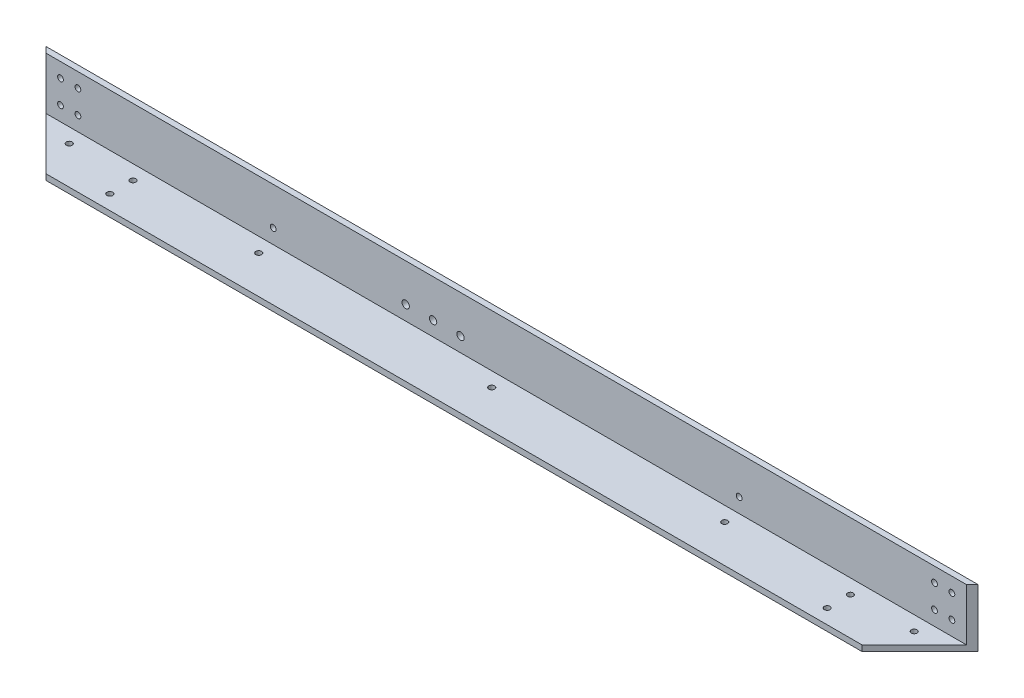
SolidWorks part; units mm, degrees
ref_plane "Front Plane" through (0, 0, 0) normal (0, 0, 1) x (1, 0, 0)
ref_plane "Top Plane" through (0, 0, 0) normal (0, 1, 0) x (1, 0, 0)
ref_plane "Right Plane" through (0, 0, 0) normal (1, 0, 0) x (0, 0, -1)
sketch "Sketch1" plane through (0, 0, 0) normal (1, 0, 0) x (0, 0, -1)
  line L0 (0, 0) -> (-31.75, 0)
  line L1 (-31.75, 0) -> (-31.75, 3.175)
  line L2 (-31.75, 3.175) -> (-3.175, 3.175)
  line L3 (-3.175, 3.175) -> (-3.175, 31.75)
  line L4 (-3.175, 31.75) -> (0, 31.75)
  line L5 (0, 31.75) -> (0, 0)
  dimension "LHeight" = 31.75
  dimension "LWidth" = 31.75
  dimension "LMaterialThickness" = 3.175
  dimension "D1" = 28.575
  dimension "D2" = 28.575
  dimension "D3" = 3.175
extrude "Boss-Extrude1" add sketch "Sketch1" along normal blind 510
chamfer "Chamfer6" distance 31.75 angle 45 1 edges at (510, 1.5875, 31.75)
chamfer "Chamfer7" distance 31.75 angle 45 1 edges at (0, 1.5875, 31.75)
sketch "TopHoles-Sketch3" plane through (0, 3.175, 0) normal (0, 1, 0) x (1, 0, 0)
  line L1 (478.25, -31.75) -> (31.75, -31.75) construction
  line L2 (510, 0) -> (0, 0) construction
  circle A5 centre (58.7375, -23.8125) radius 1.5875
  circle A6 centre (451.2625, -23.8125) radius 1.5875
  circle A9 centre (451.2625, -11.1125) radius 1.5875
  circle A10 centre (58.7375, -11.1125) radius 1.5875
  circle A11 centre (486.1875, -11.1125) radius 1.5875
  circle A12 centre (23.8125, -11.1125) radius 1.5875
  circle A13 centre (127.5, -11.1125) radius 1.5875
  circle A14 centre (255, -11.1125) radius 1.5875
  circle A15 centre (382.5, -11.1125) radius 1.5875
  dimension "D9" = 3.175
  dimension "D12" = 7.9375
  dimension "D2" = 11.1125
  dimension "D3" = 23.8125
  dimension "D6" = 23.8125
  dimension "D4" = 12.7
  dimension "D5" = 34.925
  dimension "D7" = 34.925
  dimension "D8" = 127.5
  dimension "D10" = 127.5
  dimension "D11" = 127.5
extrude "TopHoles-Cut-Extrude2" cut sketch "TopHoles-Sketch3" against normal through all
sketch "SideHoles-Sketch4" plane through (0, 0, 3.175) normal (0, 0, 1) x (1, 0, 0)
  line L0 (0, 0) -> (0, 31.75) construction
  line L1 (510, 0) -> (510, 31.75) construction
  line L2 (478.25, 0) -> (31.75, 0) construction
  line L7 (510, 0) -> (0, 0) construction
  line L8 (510, 31.75) -> (0, 31.75) construction
  circle A1 centre (11.1125, 23.8125) radius 1.5875
  circle A3 centre (489.3625, 23.8125) radius 1.5875
  circle A4 centre (20.6375, 23.8125) radius 1.5875
  circle A5 centre (498.8875, 23.8125) radius 1.5875
  circle A6 centre (11.1125, 11.1125) radius 1.5875
  circle A7 centre (20.6375, 11.1125) radius 1.5875
  circle A8 centre (489.3625, 11.1125) radius 1.5875
  circle A9 centre (498.8875, 11.1125) radius 1.5875
  circle A10 centre (200, 11.1125) radius 2
  circle A11 centre (215, 11.1125) radius 2
  circle A12 centre (230, 11.1125) radius 2
  circle A13 centre (127.5, 11.1125) radius 1.5875
  circle A14 centre (382.5, 11.1125) radius 1.5875
  dimension "D2" = 3.175
  dimension "D11" = 4
  dimension "D7" = 11.1125
  dimension "D4" = 7.9375
  dimension "D1" = 11.1125
  dimension "D6" = 20.6375
  dimension "D3" = 11.1125
  dimension "D5" = 20.6375
  dimension "D8" = 215
  dimension "D9" = 15
  dimension "D10" = 15
  dimension "D12" = 11.1125
  dimension "D13" = 127.5
  dimension "D14" = 127.5
extrude "SideHoles-Cut-Extrude3" cut sketch "SideHoles-Sketch4" against normal through all
equation "\"TopRailWidth\"= 1.25in"
equation "\"TopRailHeight\"= 1.25in"
equation "\"RailThickness\"= .125in'Spec"
equation "\"SideRailHoleY1FromEdge\"= \"HoleOffsetFromEdge\""
equation "\"SideRailHoleX1FromSide\"= \"HoleOffsetFromSide\""
equation "\"VSWidth\"= 1.25in'Spec"
equation "\"HoleOffsetFromEdge\"= \"RailThickness\" * 2.5"
equation "\"HoleOffsetFromSide\"= \"RailThickness\" * 3.5"
equation "\"TopCBWidth\"= \"TopRailWidth\" - \"RailThickness\"'Equals 28.575"
equation "\"SideRailHoleX2FromSide\"= \"VSWidth\" - \"HoleOffsetFromEdge\" - \"RailThickness\"'Equals 20.6375"
equation "\"FasteningHoleDiameter\"= .125in"
equation "\"SideRailHoleY2FromSide\"= \"HoleOffsetFromSide\""
equation "\"D2@SideHoles-Sketch4\"=\"FasteningHoleDiameter\""
equation "\"LWidth@Sketch1\"=\"TopRailWidth\""
equation "\"LHeight@Sketch1\"=\"TopRailHeight\""
equation "\"LMaterialThickness@Sketch1\"=\"RailThickness\""
equation "\"D1@Boss-Extrude1\"= \"FrontBackRailLength\""
equation "\"FrontBackRailLength\"= 510mm"
equation "\"D7@SideHoles-Sketch4\"=\"SideRailHoleY2FromSide\""
equation "\"D4@SideHoles-Sketch4\"=\"SideRailHoleY1FromEdge\""
equation "\"D1@Chamfer6\"=\"TopRailWidth\""
equation "\"D1@Chamfer7\"=\"TopRailWidth\""
equation "\"D6@TopHoles-Sketch3\"=\"TopHoleX1FromEdge\" + \"RailThickness\""
equation "\"D1@SideHoles-Sketch4\"=\"SideRailHoleX1FromSide\""
equation "\"D6@SideHoles-Sketch4\"=\"SideRailHoleX2FromSide\""
equation "\"D5@SideHoles-Sketch4\"=\"SideRailHoleX2FromSide\""
equation "\"D3@SideHoles-Sketch4\" = \"SideRailHoleX1FromSide\""
equation "\"D8@SideHoles-Sketch4\"=\"FrontBackRailLength\"/2 - 40mm"
equation "\"TopHoleX1FromEdge\"= \"TopCBWidth\" - \"HoleOffsetFromEdge\"'Equals 20.6375"
equation "\"TopHoleX2FromX1\"= \"TopCBLength\" - \"TopHoleX1FromEdge\" - \"HoleOffsetFromEdge\"'Equals 34.925"
equation "\"TopHoleY1FromSide\"= \"HoleOffsetFromSide\""
equation "\"TopHoleY2FromY1\"= \"TopCBWidth\" - \"TopHoleY1FromEdge\" - \"HoleOffsetFromEdge\"'Equals 12.7"
equation "\"D2@TopHoles-Sketch3\"=\"TopHoleY1FromSide\""
equation "\"D4@TopHoles-Sketch3\"=\"TopHoleY2FromY1\""
equation "\"D5@TopHoles-Sketch3\"=\"TopHoleX2FromX1\""
equation "\"D7@TopHoles-Sketch3\"=\"TopHoleX2FromX1\""
equation "\"TopCBLength\"= \"TopRailWidth\" * 2'Equals 63.5"
equation "\"TopHoleY1FromEdge\"= \"HoleOffsetFromEdge\""
equation "\"D3@TopHoles-Sketch3\"=\"TopHoleX1FromEdge\" + \"RailThickness\""
equation "\"FrontOrBackEnclosureOffsets\"= \"FrontBackRailLength\" / 4"
equation "\"D8@TopHoles-Sketch3\"=\"FrontOrBackEnclosureOffsets\""
equation "\"D11@TopHoles-Sketch3\"=\"FrontOrBackEnclosureOffsets\""
equation "\"D10@TopHoles-Sketch3\"=\"FrontOrBackEnclosureOffsets\""
equation "\"D13@SideHoles-Sketch4\"=\"FrontOrBackEnclosureOffsets\""
equation "\"D14@SideHoles-Sketch4\"=\"FrontOrBackEnclosureOffsets\""
